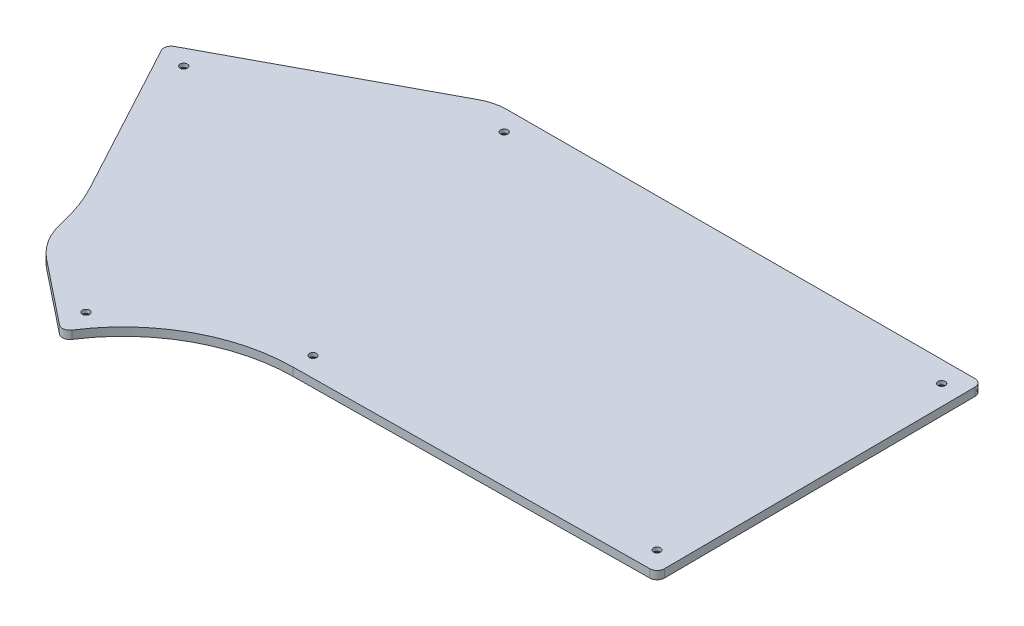
SolidWorks part; units mm, degrees
ref_plane "Front Plane" through (0, 0, 0) normal (0, 0, 1) x (1, 0, 0)
ref_plane "Top Plane" through (0, 0, 0) normal (0, 1, 0) x (1, 0, 0)
ref_plane "Right Plane" through (0, 0, 0) normal (1, 0, 0) x (0, 0, -1)
sketch "Sketch1" plane through (0, 0, 0) normal (0, 1, 0) x (1, 0, 0)
  line L24 (134.1615, 59.4328) -> (-37.7889, 59.0599)
  line L25 (137.6528, -58.3822) -> (136.9041, 56.7189)
  line L26 (4.8493, -62.4702) -> (134.9902, -61.086)
  line L27 (-74.8545, -73.4415) -> (-51.54, -92.0086)
  line L28 (-46.2425, 56.9344) -> (-119.2144, 17.9136)
  line L29 (-120.3052, 14.2556) -> (-89.8302, -42.2964)
  line L30 (134.1615, 59.4328) -> (-37.7889, 59.0599)
  line L31 (137.6528, -58.3822) -> (136.9041, 56.7189)
  line L32 (4.8493, -62.4702) -> (134.9902, -61.086)
  line L33 (-74.8545, -73.4415) -> (-51.54, -92.0086)
  line L34 (-46.2425, 56.9344) -> (-119.2144, 17.9136)
  line L35 (-120.3052, 14.2556) -> (-89.8302, -42.2964)
  circle A24 centre (129.6277, 51.7264) radius 1.35
  circle A25 centre (129.6277, 51.7264) radius 1.35 construction
  circle A26 centre (-31.1645, 51.3776) radius 1.35
  circle A27 centre (-111.1712, 13.3696) radius 1.35
  circle A28 centre (-50.6586, -83.1199) radius 1.35
  circle A29 centre (4.9474, -55.1276) radius 1.35
  circle A30 centre (130.3141, -53.7942) radius 1.35
  spline S16 degree 3 poles (-1750.0342, -948.8268) (130.2961, -180.8193) (13.4597, 72.508) (-42.8647, 58.3355) (-43.5648, 58.1135) (-131.0806, 24.2976) (50.3404, -686.9456) (424.0706, -1884.0181) knots -19.003901 -19.003901 -19.003901 -19.003901 0.5 0.5 0.75 0.75 32.588849 32.588849 32.588849 32.588849 only from (-37.7889, 59.0599) to (-46.2425, 56.9344)
  spline S17 degree 3 poles (-1821.6728, -347.1153) (-36.9477, -11.1516) (140.585, 39.158) (136.8119, 57.4234) (136.7584, 57.5961) (136.6192, 57.9249) (136.5344, 58.0808) (136.3347, 58.3756) (136.2188, 58.5151) (135.9661, 58.7651) (135.8285, 58.8772) (135.53, 59.0752) (135.3712, 59.1593) (121.6315, 64.8161) (57.2507, -38.1692) (1891.3486, -890.8517) knots -12.883613 -12.883613 -12.883613 -12.883613 0.125 0.125 0.25 0.25 0.375 0.375 0.5 0.5 0.625 0.625 0.75 0.75 11.095935 11.095935 11.095935 11.095935 only from (136.9041, 56.7189) to (134.1615, 59.4328)
  spline S18 degree 3 poles (-276.4324, 1895.861) (62.9344, 125.8014) (116.8113, -64.9114) (135.6835, -60.9939) (135.8534, -60.9413) (136.1772, -60.8044) (136.3306, -60.7209) (136.6206, -60.5245) (136.7579, -60.4103) (137.0036, -60.1612) (137.1137, -60.0254) (137.3075, -59.7312) (137.3897, -59.5743) (142.9509, -45.8759) (38.1439, 18.2052) (-733.4382, -1856.1153) knots -13.53973 -13.53973 -13.53973 -13.53973 0.125 0.125 0.25 0.25 0.375 0.375 0.5 0.5 0.625 0.625 0.75 0.75 11.207601 11.207601 11.207601 11.207601 only from (134.9902, -61.086) to (137.6528, -58.3822)
  spline S19 degree 3 poles (1184.8598, -1655.2654) (130.7733, -592.8399) (-132.1522, -191.7787) (-41.2747, -83.0887) (-39.4846, -81.1975) (-35.653, -77.626) (-33.6466, -75.9781) (-29.4595, -72.9472) (-27.2788, -71.5642) (-23.8764, -69.6894) (-22.7204, -69.0977) (-20.3635, -67.9827) (-19.1598, -67.4584) (-15.5298, -66.0093) (-10.6111, -64.3915) (-5.5395, -63.3851) (-1.6775, -62.8634) (-0.3794, -62.7282) (199.3462, -48.2135) (438.9032, -971.5) (680.2854, -1936.3921) knots -6.564083 -6.564083 -6.564083 -6.564083 0.125 0.125 0.25 0.25 0.375 0.375 0.5 0.5 0.5625 0.5625 0.625 0.625 0.75 0.875 0.875 0.9375 0.9375 10.43419 10.43419 10.43419 10.43419 only from (-47.5713, -91.3749) to (4.8493, -62.4702)
  spline S20 degree 3 poles (856.5661, 1689.5375) (35.357, 155.1076) (-70.6412, -82.453) (-50.8969, -92.3974) (-50.7176, -92.4657) (-50.3532, -92.5624) (-50.1678, -92.5917) (-49.7905, -92.6117) (-49.5996, -92.6018) (-49.2286, -92.5435) (-49.0453, -92.4949) (-48.6909, -92.3592) (-48.5235, -92.274) (-48.2079, -92.0693) (-48.0587, -91.9484) (-31.8983, -75.7333) (-229.0637, 131.0926) (-1491.9962, 1291.4631) knots -14.459821 -14.459821 -14.459821 -14.459821 0.125 0.125 0.25 0.25 0.375 0.375 0.5 0.5 0.625 0.625 0.75 0.75 0.875 0.875 15.941855 15.941855 15.941855 15.941855 only from (-51.54, -92.0086) to (-47.5713, -91.3749)
  spline S21 degree 3 poles (1715.5298, 805.2357) (413.6171, 296.7615) (-119.1705, 27.8931) (-82.0109, -64.1512) (-81.7212, -64.7879) (-81.0923, -66.0267) (-80.0727, -67.8369) (-78.8304, -69.5071) (-14.4953, -141.9585) (441.5521, 184.2419) (404.7563, 1828.5459) knots -17.322052 -17.322052 -17.322052 -17.322052 0.25 0.25 0.375 0.375 0.5 0.75 0.75 17.772745 17.772745 17.772745 17.772745 only from (-83.5017, -59.4922) to (-74.8545, -73.4415)
  spline S22 degree 3 poles (-568.191, -1942.8168) (-575.0846, 50.2444) (-132.8247, 76.428) (-28.3991, -207.3557) (-587.8232, -544.294) (-1867.1202, -930.2582) knots -21.577875 -21.577875 -21.577875 -21.577875 0.5 0.5 27.71554 27.71554 27.71554 27.71554 only from (-89.8302, -42.2964) to (-83.5017, -59.4922)
  spline S23 degree 3 poles (1156.1577, -1522.3099) (71.1894, -158.2431) (-103.0248, 31.3004) (-119.7897, 17.5078) (-119.9163, 17.3809) (-120.1399, 17.1067) (-120.237, 16.9601) (-120.4021, 16.6481) (-120.4699, 16.4817) (-120.5702, 16.1442) (-120.6036, 15.9713) (-120.6363, 15.6175) (-120.635, 15.4398) (-120.5985, 15.09) (-120.563, 14.9156) (-111.4748, -14.5397) (374.9159, 146.9258) (1768.3529, 670.8468) knots -15.177208 -15.177208 -15.177208 -15.177208 0.125 0.125 0.25 0.25 0.375 0.375 0.5 0.5 0.625 0.625 0.75 0.75 0.875 0.875 22.431731 22.431731 22.431731 22.431731 only from (-119.2144, 17.9136) to (-120.3052, 14.2556)
  spline S24 degree 3 poles (-37.7889, 59.0599) (-39.2604, 59.0567) (-40.7263, 58.8736) (-42.8647, 58.3355) (-43.5648, 58.1135) (-44.9284, 57.5866) (-45.5937, 57.2813) (-46.2425, 56.9344) knots 0 0 0 0 0.5 0.5 0.75 0.75 1 1 1 1
  spline S25 degree 3 poles (136.9041, 56.7189) (136.9029, 56.8989) (136.8838, 57.0757) (136.8119, 57.4234) (136.7584, 57.5961) (136.6192, 57.9249) (136.5344, 58.0808) (136.3347, 58.3756) (136.2188, 58.5151) (135.9661, 58.7651) (135.8285, 58.8772) (135.53, 59.0752) (135.3712, 59.1593) (134.8791, 59.3619) (134.5214, 59.4336) (134.1615, 59.4328) knots 0 0 0 0 0.125 0.125 0.25 0.25 0.375 0.375 0.5 0.5 0.625 0.625 0.75 0.75 1 1 1 1
  spline S26 degree 3 poles (134.9902, -61.086) (135.1673, -61.0842) (135.3414, -61.0649) (135.6835, -60.9939) (135.8534, -60.9413) (136.1772, -60.8044) (136.3306, -60.7209) (136.6206, -60.5245) (136.7579, -60.4103) (137.0036, -60.1612) (137.1137, -60.0254) (137.3075, -59.7312) (137.3897, -59.5743) (137.5868, -59.0889) (137.6551, -58.7364) (137.6528, -58.3822) knots 0 0 0 0 0.125 0.125 0.25 0.25 0.375 0.375 0.5 0.5 0.625 0.625 0.75 0.75 1 1 1 1
  spline S27 degree 3 poles (-47.5713, -91.3749) (-46.153, -89.173) (-44.6089, -87.0764) (-41.2747, -83.0887) (-39.4846, -81.1975) (-35.653, -77.626) (-33.6466, -75.9781) (-29.4595, -72.9472) (-27.2788, -71.5642) (-23.8764, -69.6894) (-22.7204, -69.0977) (-20.3635, -67.9827) (-19.1598, -67.4584) (-15.5298, -66.0093) (-10.6111, -64.3915) (-5.5395, -63.3851) (-1.6775, -62.8634) (-0.3794, -62.7282) (2.2323, -62.5384) (3.5399, -62.4841) (4.8493, -62.4702) knots 0 0 0 0 0.125 0.125 0.25 0.25 0.375 0.375 0.5 0.5 0.5625 0.5625 0.625 0.625 0.75 0.875 0.875 0.9375 0.9375 1 1 1 1
  spline S28 degree 3 poles (-51.54, -92.0086) (-51.391, -92.1272) (-51.2324, -92.2284) (-50.8969, -92.3974) (-50.7176, -92.4657) (-50.3532, -92.5624) (-50.1678, -92.5917) (-49.7905, -92.6117) (-49.5996, -92.6018) (-49.2286, -92.5435) (-49.0453, -92.4949) (-48.6909, -92.3592) (-48.5235, -92.274) (-48.2079, -92.0693) (-48.0587, -91.9484) (-47.7928, -91.6815) (-47.6745, -91.535) (-47.5713, -91.3749) knots 0 0 0 0 0.125 0.125 0.25 0.25 0.375 0.375 0.5 0.5 0.625 0.625 0.75 0.75 0.875 0.875 1 1 1 1
  spline S29 degree 3 poles (-83.5017, -59.4922) (-83.2079, -60.8646) (-82.7983, -62.2008) (-82.0109, -64.1512) (-81.7212, -64.7879) (-81.0923, -66.0267) (-80.0727, -67.8369) (-78.8304, -69.5071) (-76.9681, -71.6044) (-75.9523, -72.5673) (-74.8545, -73.4415) knots 0 0 0 0 0.25 0.25 0.375 0.375 0.5 0.75 0.75 1 1 1 1
  spline S30 degree 3 poles (-89.8302, -42.2964) (-88.3751, -44.9966) (-87.1131, -47.7965) (-84.9946, -53.5535) (-84.1437, -56.4929) (-83.5017, -59.4922) knots 0 0 0 0 0.5 0.5 1 1 1 1
  spline S31 degree 3 poles (-119.2144, 17.9136) (-119.3717, 17.8295) (-119.5181, 17.7313) (-119.7897, 17.5078) (-119.9163, 17.3809) (-120.1399, 17.1067) (-120.237, 16.9601) (-120.4021, 16.6481) (-120.4699, 16.4817) (-120.5702, 16.1442) (-120.6036, 15.9713) (-120.6363, 15.6175) (-120.635, 15.4398) (-120.5985, 15.09) (-120.563, 14.9156) (-120.4582, 14.576) (-120.3898, 14.4126) (-120.3052, 14.2556) knots 0 0 0 0 0.125 0.125 0.25 0.25 0.375 0.375 0.5 0.5 0.625 0.625 0.75 0.75 0.875 0.875 1 1 1 1
  dimension "D1" = 0.5
extrude "Boss-Extrude1" add sketch "Sketch1" against normal blind 3
sketch "Sketch2" plane through (0, -3, 0) normal (0, -1, 0) x (1, 0, 0)
  circle A0 centre (-50.6586, 83.1199) radius 2.5
  circle A1 centre (4.9474, 55.1276) radius 2.5
  circle A2 centre (130.3141, 53.7942) radius 2.5
  circle A3 centre (129.6277, -51.7264) radius 2.5
  circle A4 centre (-31.1645, -51.3776) radius 2.5
  circle A5 centre (-111.1712, -13.3696) radius 2.5
  dimension "D1" = 5
extrude "Cut-Extrude1" cut sketch "Sketch2" against normal blind 1.7
chamfer "Chamfer1" distance 1.2 angle 45 6 edges at (129.6277, -1.3, -54.2264) (130.3141, -1.3, 51.2942) (4.9474, -1.3, 52.6276) (-50.6586, -1.3, 80.6199) (-111.1712, -1.3, -15.8696) (-31.1645, -1.3, -53.8776)
